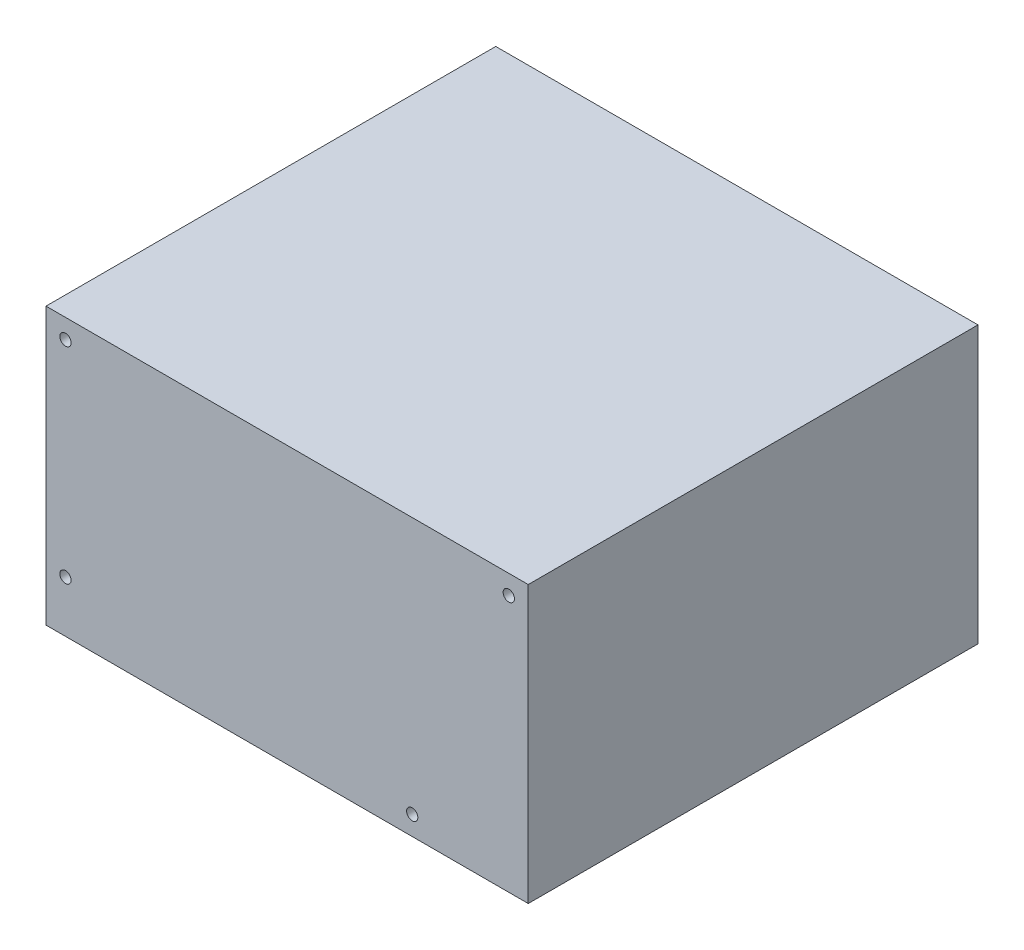
SolidWorks part; units mm, degrees
ref_plane "정면" through (0, 0, 0) normal (0, 0, 1) x (1, 0, 0)
ref_plane "윗면" through (0, 0, 0) normal (0, 1, 0) x (1, 0, 0)
ref_plane "우측면" through (0, 0, 0) normal (1, 0, 0) x (0, 0, -1)
sketch "스케치1" plane through (0, 0, 0) normal (0, 0, 1) x (1, 0, 0)
  line L0 (75.057, 86) -> (75.057, 0) construction
  line L1 (0, 0) -> (150.114, 0)
  line L2 (0, 0) -> (0, 86)
  line L3 (0, 86) -> (150.114, 86)
  line L4 (150.114, 0) -> (150.114, 86)
  line L5 (6.0579, 80) -> (144.0561, 80) construction
  line L6 (6.0579, 80) -> (6.0579, 16) construction
  line L7 (6.0579, 16) -> (144.0561, 16) construction
  line L8 (144.0561, 80) -> (144.0561, 16) construction
  circle A0 centre (6.0579, 80) radius 1.7526
  circle A1 centre (144.0561, 80) radius 1.7526
  circle A2 centre (6.0579, 16) radius 1.7526
  circle A3 centre (114, 6) radius 1.7526
  point P16 (75.057, 80)
  dimension "D7" = 3.5052
  dimension "D1" = 150.114
  dimension "D2" = 86
  dimension "D3" = 64
  dimension "D4" = 16
  dimension "D5" = 137.9982
  dimension "D8" = 114
  dimension "D9" = 6
extrude "보스-돌출1" add sketch "스케치1" against normal blind 140 contours A3 | L1 L4 L3 L2 A3 A2 A1 A0 | A1 | A2 | A0 region at (75.0795, 42.9925, 0) region at (6.0579, 80, 0) region at (144.0561, 80, 0) region at (6.0579, 16, 0) region at (114, 6, 0)
extrude "컷-돌출1" cut sketch "스케치1<3>" against normal blind 127 contours A0 | A1 | A2 | A3 region at (6.0579, 80, 0) region at (144.0561, 80, 0) region at (6.0579, 16, 0) region at (114, 6, 0)
sketch "스케치1<3>" plane through (0, 0, 0) normal (0, 0, 1) x (1, 0, 0) same geometry as "스케치1"
